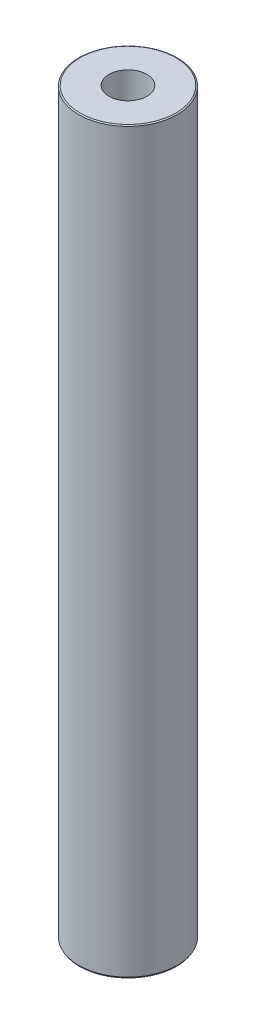
SolidWorks part; units mm, degrees
ref_plane "Front Plane" through (0, 0, 0) normal (0, 0, 1) x (1, 0, 0)
ref_plane "Top Plane" through (0, 0, 0) normal (0, 1, 0) x (1, 0, 0)
ref_plane "Right Plane" through (0, 0, 0) normal (1, 0, 0) x (0, 0, -1)
sketch "Sketch1" plane through (0, 0, 0) normal (0, 1, 0) x (1, 0, 0)
  circle A0 centre (0, 0) radius 40
  dimension "SHAFT_OD" = 80
extrude "Boss-Extrude1" add sketch "Sketch1" along normal blind 600
sketch "Sketch2" plane through (0, 0, 0) normal (0, 1, 0) x (1, 0, 0)
  circle A0 centre (0, 0) radius 15.4168
  dimension "BORE_D" = 30.8335
extrude "Cut-Extrude1" cut sketch "Sketch2" along normal through all
chamfer "Chamfer1" distance 0.6037 angle 60 2 edges at (0, 600, 40) (0, 0, 40) first distance on face at (0, 600, 40) first distance on face at (0, 0, 15.4168)
